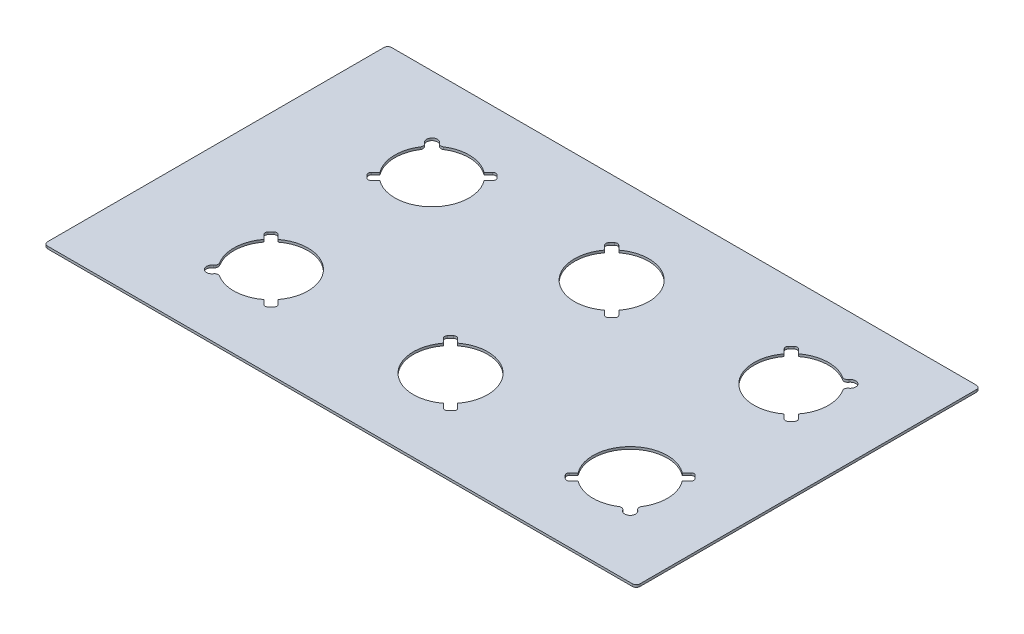
SolidWorks part; units mm, degrees
material "Hexcel AS4C (3000 Filaments)"
ref_plane "Front" through (0, 0, 0) normal (0, 0, 1) x (1, 0, 0)
ref_plane "Top" through (0, 0, 0) normal (0, 1, 0) x (1, 0, 0)
ref_plane "Right" through (0, 0, 0) normal (1, 0, 0) x (0, 0, -1)
sketch "Sketch1" plane through (0, 0, 0) normal (0, 1, 0) x (1, 0, 0)
  line L1 (-184.15, -114.3) -> (184.15, -114.3)
  line L2 (-184.15, -114.3) -> (-184.15, 114.3)
  line L3 (-184.15, 114.3) -> (184.15, 114.3)
  line L4 (184.15, -114.3) -> (184.15, 114.3)
  line L5 (-184.15, -114.3) -> (184.15, 114.3) construction
  line L6 (-184.15, 114.3) -> (184.15, -114.3) construction
  point P0 (0, 0)
  dimension "D1" = 368.3
  dimension "D2" = 228.6
extrude "Boss-Extrude1" add sketch "Sketch1" along normal blind 1.5748
sketch "Sketch2" plane through (-184.15, 0, 0) normal (-1, 0, 0) x (0, 0, 1)
  line L1 (114.3, 0) -> (-114.3, 0)
  line L2 (114.3, 0) -> (114.3, 1.5748)
  line L3 (114.3, 1.5748) -> (-114.3, 1.5748)
  line L4 (-114.3, 0) -> (-114.3, 1.5748)
extrude "Boss-Extrude2" add sketch "Sketch2" along normal blind 25.4
sketch "Sketch3" plane through (0, 0, 0) normal (0, -1, 0) x (1, 0, 0)
  line L0 (96.8413, -71.3316) -> (99.493, -68.6799) construction
  line L1 (141.9187, -35.7294) -> (139.267, -38.3811) construction
  line L2 (140.0095, -30.9918) -> (141.9187, -32.901) construction
  line L3 (134.5294, -33.6435) -> (137.1811, -30.9918) construction
  line L4 (104.2306, -73.4175) -> (101.5789, -76.0692) construction
  line L5 (98.7505, -76.0692) -> (96.8413, -74.16) construction
  line L6 (141.9187, -35.7294) -> (139.054, -38.5941)
  line L7 (140.0095, -30.9918) -> (141.9187, -32.901)
  line L8 (134.3164, -33.8565) -> (137.1811, -30.9918)
  line L9 (104.4436, -73.2045) -> (101.5789, -76.0692)
  line L10 (98.7505, -76.0692) -> (96.8413, -74.16)
  line L11 (96.8413, -71.3316) -> (99.706, -68.4669)
  line L12 (22.5387, -35.7294) -> (19.887, -38.3811) construction
  line L13 (20.6295, -30.9918) -> (22.5387, -32.901) construction
  line L14 (15.1494, -33.6435) -> (17.8011, -30.9918) construction
  line L15 (-22.5387, -71.3316) -> (-19.887, -68.6799) construction
  line L16 (-20.6295, -76.0692) -> (-22.5387, -74.16) construction
  line L17 (-15.1494, -73.4175) -> (-17.8011, -76.0692) construction
  line L18 (22.5387, -35.7294) -> (19.674, -38.5941)
  line L19 (20.6295, -30.9918) -> (22.5387, -32.901)
  line L20 (14.9364, -33.8565) -> (17.8011, -30.9918)
  line L21 (-22.5387, -71.3316) -> (-19.674, -68.4669)
  line L22 (-20.6295, -76.0692) -> (-22.5387, -74.16)
  line L23 (-14.9364, -73.2045) -> (-17.8011, -76.0692)
  line L24 (-137.1811, -30.9918) -> (-134.5294, -33.6435) construction
  line L25 (-141.9187, -32.901) -> (-140.0095, -30.9918) construction
  line L26 (-139.267, -38.3811) -> (-141.9187, -35.7294) construction
  line L27 (-99.493, -68.6799) -> (-96.8413, -71.3316) construction
  line L28 (-96.8413, -74.16) -> (-98.7505, -76.0692) construction
  line L29 (-101.5789, -76.0692) -> (-104.2306, -73.4175) construction
  line L30 (-137.1811, -30.9918) -> (-134.3164, -33.8565)
  line L31 (-141.9187, -32.901) -> (-140.0095, -30.9918)
  line L32 (-139.054, -38.5941) -> (-141.9187, -35.7294)
  line L33 (-99.706, -68.4669) -> (-96.8413, -71.3316)
  line L34 (-96.8413, -74.16) -> (-98.7505, -76.0692)
  line L35 (-101.5789, -76.0692) -> (-104.4436, -73.2045)
  line L36 (-134.5294, 33.6435) -> (-137.1811, 30.9918) construction
  line L37 (-140.0095, 30.9918) -> (-141.9187, 32.901) construction
  line L38 (-141.9187, 35.7294) -> (-139.267, 38.3811) construction
  line L39 (-96.8413, 71.3316) -> (-99.493, 68.6799) construction
  line L40 (-98.7505, 76.0692) -> (-96.8413, 74.16) construction
  line L41 (-104.2306, 73.4175) -> (-101.5789, 76.0692) construction
  line L42 (-134.3164, 33.8565) -> (-137.1811, 30.9918)
  line L43 (-140.0095, 30.9918) -> (-141.9187, 32.901)
  line L44 (-141.9187, 35.7294) -> (-139.054, 38.5941)
  line L45 (-96.8413, 71.3316) -> (-99.706, 68.4669)
  line L46 (-98.7505, 76.0692) -> (-96.8413, 74.16)
  line L47 (-104.4436, 73.2045) -> (-101.5789, 76.0692)
  line L48 (15.1494, 73.4175) -> (17.8011, 76.0692) construction
  line L49 (20.6295, 76.0692) -> (22.5387, 74.16) construction
  line L50 (22.5387, 71.3316) -> (19.887, 68.6799) construction
  line L51 (-20.6295, 30.9918) -> (-22.5387, 32.901) construction
  line L52 (-15.1494, 33.6435) -> (-17.8011, 30.9918) construction
  line L53 (-22.5387, 35.7294) -> (-19.887, 38.3811) construction
  line L54 (14.9364, 73.2045) -> (17.8011, 76.0692)
  line L55 (20.6295, 76.0692) -> (22.5387, 74.16)
  line L56 (22.5387, 71.3316) -> (19.674, 68.4669)
  line L57 (-20.6295, 30.9918) -> (-22.5387, 32.901)
  line L58 (-14.9364, 33.8565) -> (-17.8011, 30.9918)
  line L59 (-22.5387, 35.7294) -> (-19.674, 38.5941)
  line L60 (101.5789, 76.0692) -> (104.2306, 73.4175) construction
  line L61 (96.8413, 74.16) -> (98.7505, 76.0692) construction
  line L62 (99.493, 68.6799) -> (96.8413, 71.3316) construction
  line L63 (139.267, 38.3811) -> (141.9187, 35.7294) construction
  line L64 (141.9187, 32.901) -> (140.0095, 30.9918) construction
  line L65 (137.1811, 30.9918) -> (134.5294, 33.6435) construction
  line L66 (101.5789, 76.0692) -> (104.4436, 73.2045)
  line L67 (96.8413, 74.16) -> (98.7505, 76.0692)
  line L68 (99.706, 68.4669) -> (96.8413, 71.3316)
  line L69 (139.054, 38.5941) -> (141.9187, 35.7294)
  line L70 (141.9187, 32.901) -> (140.0095, 30.9918)
  line L71 (137.1811, 30.9918) -> (134.3164, 33.8565)
  arc A0 (104.4436, -73.2045) -> (139.054, -38.5941) centre (119.38, -53.5305) ccw
  arc A2 (-14.9364, -73.2045) -> (19.674, -38.5941) centre (0, -53.5305) ccw
  arc A3 (-99.706, -68.4669) -> (-134.3164, -33.8565) centre (-119.38, -53.5305) ccw
  arc A4 (-134.3164, 33.8565) -> (-99.706, 68.4669) centre (-119.38, 53.5305) ccw
  arc A5 (-14.9364, 33.8565) -> (19.674, 68.4669) centre (0, 53.5305) ccw
  arc A6 (139.054, 38.5941) -> (104.4436, 73.2045) centre (119.38, 53.5305) ccw
  arc A7 (96.8413, -71.3316) -> (96.8413, -74.16) centre (98.2555, -72.7458) ccw construction
  arc A8 (141.9187, -35.7294) -> (141.9187, -32.901) centre (140.5045, -34.3152) ccw construction
  arc A9 (140.0095, -30.9918) -> (137.1811, -30.9918) centre (138.5953, -32.406) ccw construction
  arc A10 (98.7505, -76.0692) -> (101.5789, -76.0692) centre (100.1647, -74.655) ccw construction
  arc A11 (141.9187, -35.7294) -> (141.9187, -32.901) centre (140.5045, -34.3152) ccw
  arc A12 (140.0095, -30.9918) -> (137.1811, -30.9918) centre (138.5953, -32.406) ccw
  arc A13 (98.7505, -76.0692) -> (101.5789, -76.0692) centre (100.1647, -74.655) ccw
  arc A14 (96.8413, -71.3316) -> (96.8413, -74.16) centre (98.2555, -72.7458) ccw
  arc A15 (134.3164, -33.8565) -> (99.706, -68.4669) centre (119.38, -53.5305) ccw
  arc A16 (22.5387, -35.7294) -> (22.5387, -32.901) centre (21.1245, -34.3152) ccw construction
  arc A17 (20.6295, -30.9918) -> (17.8011, -30.9918) centre (19.2153, -32.406) ccw construction
  arc A18 (-22.5387, -71.3316) -> (-22.5387, -74.16) centre (-21.1245, -72.7458) ccw construction
  arc A19 (-20.6295, -76.0692) -> (-17.8011, -76.0692) centre (-19.2153, -74.655) ccw construction
  arc A20 (22.5387, -35.7294) -> (22.5387, -32.901) centre (21.1245, -34.3152) ccw
  arc A21 (20.6295, -30.9918) -> (17.8011, -30.9918) centre (19.2153, -32.406) ccw
  arc A22 (-22.5387, -71.3316) -> (-22.5387, -74.16) centre (-21.1245, -72.7458) ccw
  arc A23 (-20.6295, -76.0692) -> (-17.8011, -76.0692) centre (-19.2153, -74.655) ccw
  arc A24 (14.9364, -33.8565) -> (-19.674, -68.4669) centre (0, -53.5305) ccw
  arc A25 (-137.1811, -30.9918) -> (-140.0095, -30.9918) centre (-138.5953, -32.406) ccw construction
  arc A26 (-141.9187, -32.901) -> (-141.9187, -35.7294) centre (-140.5045, -34.3152) ccw construction
  arc A27 (-96.8413, -74.16) -> (-96.8413, -71.3316) centre (-98.2555, -72.7458) ccw construction
  arc A28 (-101.5789, -76.0692) -> (-98.7505, -76.0692) centre (-100.1647, -74.655) ccw construction
  arc A29 (-137.1811, -30.9918) -> (-140.0095, -30.9918) centre (-138.5953, -32.406) ccw
  arc A30 (-141.9187, -32.901) -> (-141.9187, -35.7294) centre (-140.5045, -34.3152) ccw
  arc A31 (-96.8413, -74.16) -> (-96.8413, -71.3316) centre (-98.2555, -72.7458) ccw
  arc A32 (-101.5789, -76.0692) -> (-98.7505, -76.0692) centre (-100.1647, -74.655) ccw
  arc A33 (-140.0095, 30.9918) -> (-137.1811, 30.9918) centre (-138.5953, 32.406) ccw construction
  arc A34 (-141.9187, 35.7294) -> (-141.9187, 32.901) centre (-140.5045, 34.3152) ccw construction
  arc A35 (-96.8413, 71.3316) -> (-96.8413, 74.16) centre (-98.2555, 72.7458) ccw construction
  arc A36 (-98.7505, 76.0692) -> (-101.5789, 76.0692) centre (-100.1647, 74.655) ccw construction
  arc A37 (-140.0095, 30.9918) -> (-137.1811, 30.9918) centre (-138.5953, 32.406) ccw
  arc A38 (-141.9187, 35.7294) -> (-141.9187, 32.901) centre (-140.5045, 34.3152) ccw
  arc A39 (-96.8413, 71.3316) -> (-96.8413, 74.16) centre (-98.2555, 72.7458) ccw
  arc A40 (-98.7505, 76.0692) -> (-101.5789, 76.0692) centre (-100.1647, 74.655) ccw
  arc A41 (20.6295, 76.0692) -> (17.8011, 76.0692) centre (19.2153, 74.655) ccw construction
  arc A42 (22.5387, 71.3316) -> (22.5387, 74.16) centre (21.1245, 72.7458) ccw construction
  arc A43 (-22.5387, 35.7294) -> (-22.5387, 32.901) centre (-21.1245, 34.3152) ccw construction
  arc A44 (-20.6295, 30.9918) -> (-17.8011, 30.9918) centre (-19.2153, 32.406) ccw construction
  arc A45 (20.6295, 76.0692) -> (17.8011, 76.0692) centre (19.2153, 74.655) ccw
  arc A46 (22.5387, 71.3316) -> (22.5387, 74.16) centre (21.1245, 72.7458) ccw
  arc A47 (-22.5387, 35.7294) -> (-22.5387, 32.901) centre (-21.1245, 34.3152) ccw
  arc A48 (-20.6295, 30.9918) -> (-17.8011, 30.9918) centre (-19.2153, 32.406) ccw
  arc A49 (101.5789, 76.0692) -> (98.7505, 76.0692) centre (100.1647, 74.655) ccw construction
  arc A50 (96.8413, 74.16) -> (96.8413, 71.3316) centre (98.2555, 72.7458) ccw construction
  arc A51 (141.9187, 32.901) -> (141.9187, 35.7294) centre (140.5045, 34.3152) ccw construction
  arc A52 (137.1811, 30.9918) -> (140.0095, 30.9918) centre (138.5953, 32.406) ccw construction
  arc A53 (101.5789, 76.0692) -> (98.7505, 76.0692) centre (100.1647, 74.655) ccw
  arc A54 (96.8413, 74.16) -> (96.8413, 71.3316) centre (98.2555, 72.7458) ccw
  arc A55 (141.9187, 32.901) -> (141.9187, 35.7294) centre (140.5045, 34.3152) ccw
  arc A56 (137.1811, 30.9918) -> (140.0095, 30.9918) centre (138.5953, 32.406) ccw
  arc A58 (-104.4436, 73.2045) -> (-139.054, 38.5941) centre (-119.38, 53.5305) ccw
  arc A59 (14.9364, 73.2045) -> (-19.674, 38.5941) centre (0, 53.5305) ccw
  arc A60 (99.706, 68.4669) -> (134.3164, 33.8565) centre (119.38, 53.5305) ccw
  arc A61 (-139.054, -38.5941) -> (-104.4436, -73.2045) centre (-119.38, -53.5305) ccw
  dimension "D1" = 24.7015
extrude "Cut-Extrude1" cut sketch "Sketch3" against normal through all
hole_wizard "9/32 (0.28125) Diameter Hole1" positions "Sketch4" profile "Sketch5" hole size "9/32" standard "ANSI Inch" end condition through all
sketch "Sketch4" plane through (0, 0, 0) normal (0, -1, 0) x (-1, 0, 0)
  point P0 (-139.0015, 73.152)
  point P3 (139.0015, 73.152)
  point P6 (139.0015, -73.152)
  point P9 (-139.0015, -73.152)
sketch "Sketch5" plane through (139.0015, 0, -73.152) normal (1, 0, 0) x (0, 0, -1)
  line L0 (0, 0) -> (0, 1.5748)
  line L1 (0, 1.5748) -> (3.5719, 1.5748)
  line L2 (3.5719, 1.5748) -> (3.5719, 0)
  line L5 (3.5719, 0) -> (0, 0)
  line L11 (0, -6.35) -> (0, 107.95) construction
  dimension "Thru Hole Dia." = 7.1437
  dimension "Thru Hole Depth" = 1.5748
fillet "Fillet1" radius 2.54 12 edges at (-209.55, 0.7874, -114.3) (-209.55, 0.7874, 114.3) (-138.0445, 0.7874, 69.7107) (-135.5602, 0.7874, 72.195) (-138.0445, 0.7874, -69.7107) (-135.5602, 0.7874, -72.195) (135.5602, 0.7874, -72.195) (138.0445, 0.7874, -69.7107) (138.0445, 0.7874, 69.7107) (135.5602, 0.7874, 72.195) (184.15, 0.7874, 114.3) (184.15, 0.7874, -114.3)
